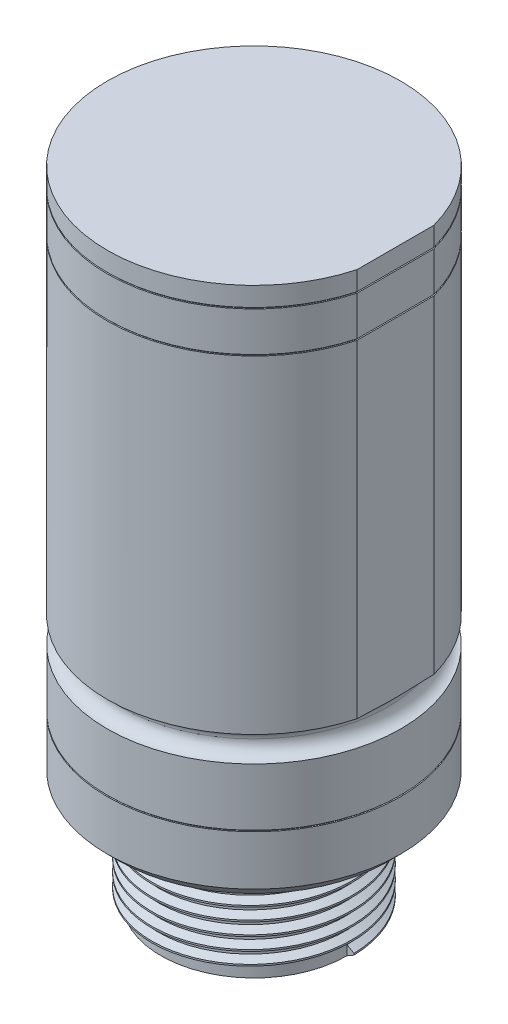
SolidWorks part; units mm, degrees
ref_plane "Front Plane" through (0, 0, 0) normal (0, 0, 1) x (1, 0, 0)
ref_plane "Top Plane" through (0, 0, 0) normal (0, 1, 0) x (1, 0, 0)
ref_plane "Right Plane" through (0, 0, 0) normal (1, 0, 0) x (0, 0, -1)
sketch "Sketch1" plane through (0, 0, 0) normal (0, 1, 0) x (1, 0, 0)
  circle A0 centre (0, 0) radius 11.5
  dimension "D1" = 23
extrude "Boss-Extrude1" add sketch "Sketch1" along normal blind 42
sketch "Sketch2" plane through (0, 0, 0) normal (0, -1, 0) x (1, 0, 0)
  circle A0 centre (0, 0) radius 7.3
  circle A1 centre (0, 0) radius 4.5
  dimension "D1" = 14.6
  dimension "D2" = 9
extrude "Boss-Extrude2" add sketch "Sketch2" along normal blind 8
thread "Thread1" pitch 1 method extrude profile "Thread Profile1" start angle 0, offset 0, length 0, pitch 1, diameter 14.6
ref_plane "Plane1" through (7.3, -8, 0) normal (0, 0, 1) x (1, 0, 0)
sketch "Thread Profile1" plane through (7.3, -8, 0) normal (0, 0, 1) x (1, 0, 0)
  line L0 (0, 0) -> (0, 1) construction
  line L1 (0, 0) -> (0.5413, 0.3125)
  line L2 (0.5413, 0.3125) -> (0.5413, 0.4375)
  line L3 (0.5413, 0.4375) -> (0, 0.75)
  line L4 (0.5413, 0.375) -> (0, 0.375) construction
  line L11 (0, 0) -> (0, 0.75)
  point P2 (0, 0)
  dimension "Pitch" = 1
  dimension "Profile_Angle" = 60
  dimension "Profile_Land" = 0.125
  dimension "Profile_Height" = 0.5413
sketch "Sketch9" plane through (0, -8, 0) normal (0, -1, 0) x (-1, 0, 0)
  circle A0 centre (0, 0) radius 7.8413
chamfer "Chamfer1" distance 1 angle 45 1 edges at (0, 0, 11.5)
ref_plane "Plane2" through (0, 9.5, 0) normal (0, 1, 0) x (1, 0, 0)
sketch "Sketch10" plane through (0, 9.5, 0) normal (0, 1, 0) x (1, 0, 0)
  circle A0 centre (0, 0) radius 10.5
  circle A2 centre (0, 0) radius 11.5
  dimension "D1" = 21
extrude "Cut-Extrude1" cut sketch "Sketch10" along normal blind 2
fillet "Fillet1" radius 1 2 edges at (0, 11.5, 10.5) (0, 9.5, 10.5)
ref_plane "Plane3" through (0, 5, 0) normal (0, 1, 0) x (1, 0, 0)
sketch "Sketch11" plane through (0, 5, 0) normal (0, 1, 0) x (1, 0, 0)
  circle A0 centre (0, 0) radius 11.5
  circle A1 centre (0, 0) radius 11.4
  circle A2 centre (0, 0) radius 11.5 construction
  dimension "D1" = 0.1
extrude "Cut-Extrude2" cut sketch "Sketch11" against normal blind 0.1
sketch "Sketch13" plane through (0, 42, 0) normal (0, 1, 0) x (1, 0, 0)
  line L1 (11.1, 3.0067) -> (11.1, -3.0067)
  arc A2 (11.1, -3.0067) -> (11.1, 3.0067) centre (0, 0) ccw
  circle A3 centre (0, 0) radius 11.5 construction
  dimension "D1" = 11.1
extrude "Cut-Extrude3" cut sketch "Sketch13" against normal up to next
ref_plane "Plane4" through (0, 40.5, 0) normal (0, 1, 0) x (1, 0, 0)
sketch "Sketch14" plane through (0, 40.5, 0) normal (0, 1, 0) x (1, 0, 0)
  line L2 (11.1, -3.0067) -> (11.1, 3.0067)
  line L3 (11.1, -3.0067) -> (11.1, 3.0067)
  line L5 (11, -2.9933) -> (11, 2.9933)
  line L6 (11, -2.9933) -> (11, 2.9933)
  arc A2 (11.1, 3.0067) -> (11.1, -3.0067) centre (0, 0) ccw
  arc A3 (11.1, 3.0067) -> (11.1, -3.0067) centre (0, 0) ccw
  arc A5 (11, 2.9933) -> (11, -2.9933) centre (0, 0) ccw
  arc A6 (11, 2.9933) -> (11, -2.9933) centre (0, 0) ccw
  dimension "D1" = 0
  dimension "D2" = 0.1
extrude "Cut-Extrude6" cut sketch "Sketch14" against normal blind 0.1
ref_plane "Plane5" through (0, 37.3, 0) normal (0, 1, 0) x (1, 0, 0)
sketch "Sketch15" plane through (0, 37.3, 0) normal (0, 1, 0) x (1, 0, 0)
  line L1 (11, -2.9933) -> (11, 2.9933)
  line L2 (11.1, -3.0067) -> (11.1, 3.0067)
  line L4 (11.1, -3.0067) -> (11.1, 3.0067)
  arc A1 (11, 2.9933) -> (11, -2.9933) centre (0, 0) ccw
  arc A2 (11.1, 3.0067) -> (11.1, -3.0067) centre (0, 0) ccw
  arc A4 (11.1, 3.0067) -> (11.1, -3.0067) centre (0, 0) ccw
  dimension "D1" = 0
  dimension "D2" = 0.1
extrude "Cut-Extrude7" cut sketch "Sketch15" against normal blind 0.1
